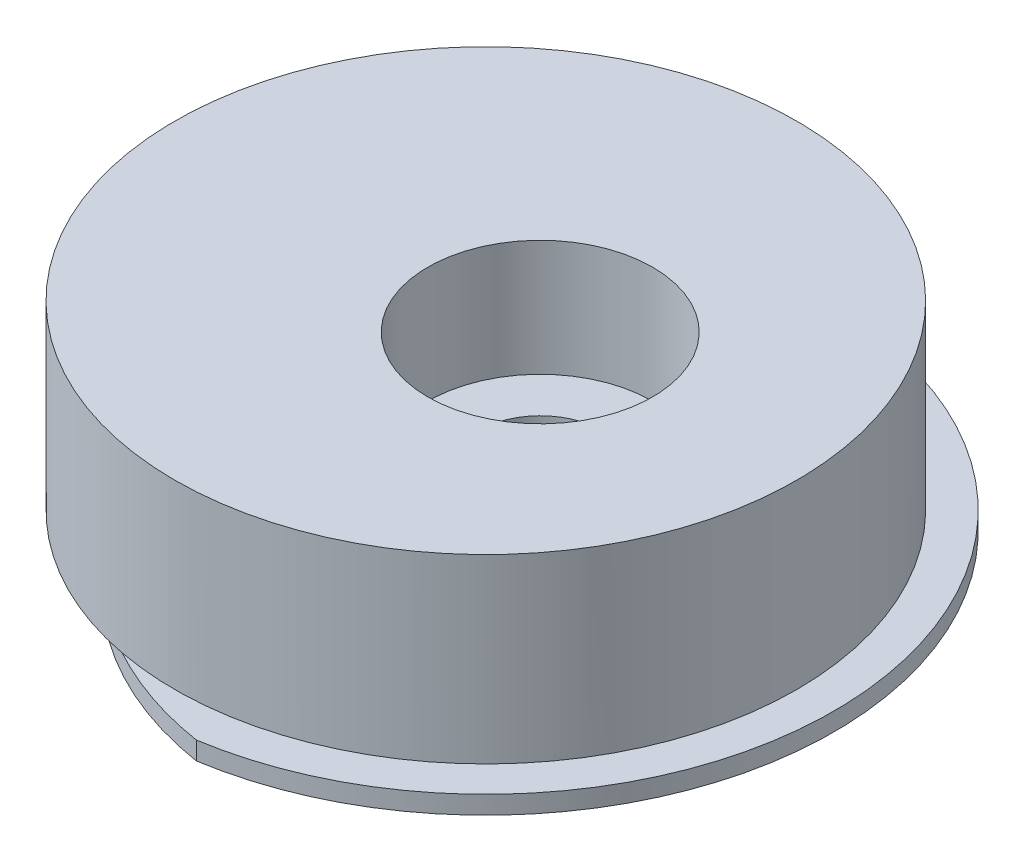
SolidWorks part; units mm, degrees
ref_plane "Front Plane" through (0, 0, 0) normal (0, 0, 1) x (1, 0, 0)
ref_plane "Top Plane" through (0, 0, 0) normal (0, 1, 0) x (1, 0, 0)
ref_plane "Right Plane" through (0, 0, 0) normal (1, 0, 0) x (0, 0, -1)
sketch "Sketch1" plane through (0, 0, 0) normal (0, 1, 0) x (1, 0, 0)
  line L0 (-1.815, 0) -> (1.815, 0) construction
  line L1 (0, -8.03) -> (0, 8.03) construction
  circle A0 centre (1.5, 0) radius 9.6
  circle A1 centre (-1.5, 0) radius 9.6
  dimension "D1" = 19.2
  dimension "D2" = 1.5
extrude "Boss-Extrude1" add sketch "Sketch1" along normal blind 0.5 contours A1 A0 region at (0, 0, 0)
sketch "Sketch2" plane through (0, 0.5, 0) normal (0, 1, 0) x (1, 0, 0)
  line L0 (-3.025, 0) -> (3.025, 0) construction
  line L1 (0, -3.025) -> (0, 3.025) construction
  circle A0 centre (-1.5, 0) radius 8.575
  dimension "D2" = 1.5
  dimension "D1" = 17.15
extrude "Boss-Extrude2" add sketch "Sketch2" along normal blind 5
sketch "Sketch3" plane through (0, 0, 0) normal (0, 1, 0) x (1, 0, 0)
  line L0 (0, -3.025) -> (0, 3.025) construction
  circle A0 centre (0, 5.8) radius 1.65
  circle A1 centre (0, -5.8) radius 1.35
  dimension "D1" = 3.3
  dimension "D3" = 2.7
  dimension "D2" = 5.8
  dimension "D4" = 5.8
extrude "Cut-Extrude1" cut sketch "Sketch3" along normal blind 4
sketch "Sketch4" plane through (0, 5.5, 0) normal (0, 1, 0) x (1, 0, 0)
  circle A0 centre (0, 0) radius 1.7
  dimension "D1" = 3.4
extrude "Cut-Extrude2" cut sketch "Sketch4" against normal through all
sketch "Sketch5" plane through (0, 5.5, 0) normal (0, 1, 0) x (1, 0, 0)
  circle A0 centre (0, 0) radius 3.1
  dimension "D1" = 6.2
extrude "Cut-Extrude3" cut sketch "Sketch5" against normal blind 3.2
equation "\"pin_circle_R\" = 27"
equation "\"ecc\" = 1.5"
equation "\"n_pins\" = 11"
equation "\"pin_d\" = 3"
equation "\"out_pin_R\" = 18.5"
equation "\"disc_clr\" = 0.1"
equation "\"seat_6803\" = 26.1"
equation "\"disc_t\" = 5"
equation "\"out_hole_clr\" = 0.5"
equation "\"boss_17\" = 17.15"
equation "\"rotor_bolt_R\" = 10"
equation "\"m25_clr\" = 2.8"
equation "\"m25_head\" = 5"
equation "\"insert_hole\" = 4.4"
equation "\"csk\" = 0.6"
equation "\"peg_d\" = 3.0"
equation "\"plug_d\" = 8.6"
equation "\"peg_clr\" = 0.3"
equation "\"m3_clr\" = 3.4"
equation "\"m3_head\" = 6.2"
equation "\"D2@Sketch1\"=\"ecc\""
equation "\"D1@Sketch2\"=\"boss_17\""
equation "\"D1@Sketch3\"=\"peg_d\"+\"peg_clr\""
equation "\"D3@Sketch3\"=\"peg_d\"-0.6+\"peg_clr\""
equation "\"D2@Sketch2\"=\"ecc\""
equation "\"D1@Sketch4\"=\"m3_clr\""
equation "\"D1@Sketch5\"=\"m3_head\""
equation "\"seat_6806\" = 42.1"
equation "\"pin_press\" = 3.2"
equation "\"pin_slip\" = 3.3"
equation "\"hub_30\" = 30.25"
equation "\"hub_short\" = 0.2"
equation "\"m3_tap\" = 2.8"
equation "\"rear_plate_t\" = 2"
